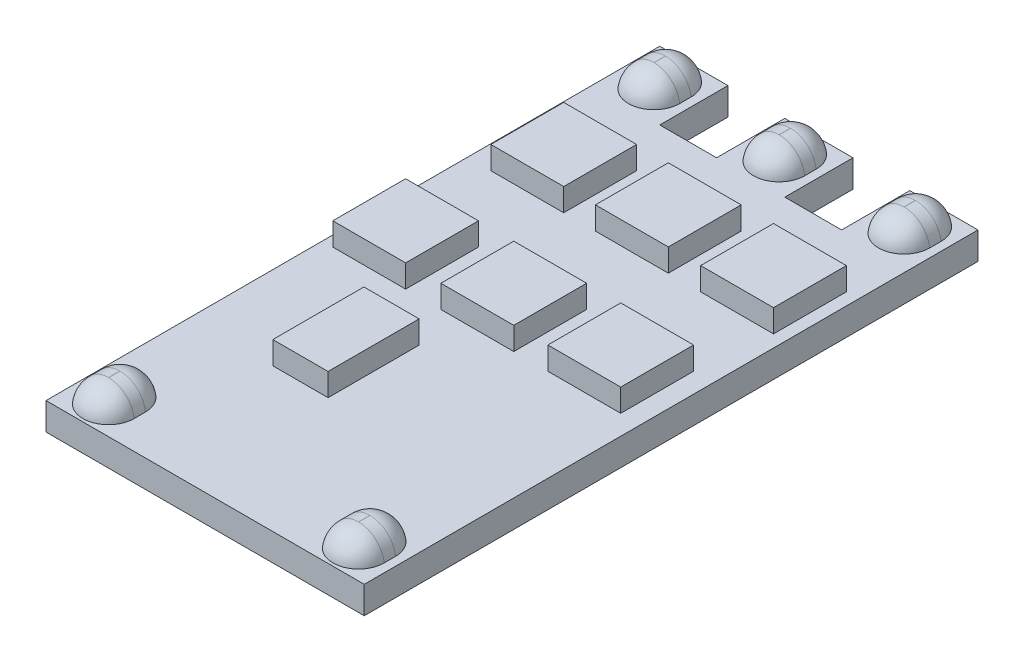
SolidWorks part; units mm, degrees
ref_plane "Front Plane" through (0, 0, 0) normal (0, 0, 1) x (1, 0, 0)
ref_plane "Top Plane" through (0, 0, 0) normal (0, 1, 0) x (1, 0, 0)
ref_plane "Right Plane" through (0, 0, 0) normal (1, 0, 0) x (0, 0, -1)
sketch "Sketch1" plane through (0, 0, 0) normal (0, 1, 0) x (1, 0, 0)
  line L0 (0, 21.6721) -> (0, -24.4888) construction
  line L1 (-7, 12) -> (7, 12)
  line L2 (-7, 12) -> (-7, -12)
  line L3 (-7, -12) -> (7, -12)
  line L4 (7, 12) -> (7, -12)
  line L5 (-7, 12) -> (7, -12) construction
  line L6 (-7, -12) -> (7, 12) construction
  line L8 (-1.5, 15) -> (1.5, 15)
  line L9 (-1.5, 15) -> (-1.5, 12)
  line L10 (-1.5, 12) -> (1.5, 12)
  line L11 (1.5, 15) -> (1.5, 12)
  line L12 (-1.5, 15) -> (1.5, 12) construction
  line L13 (-1.5, 12) -> (1.5, 15) construction
  line L14 (-7, 12) -> (-4, 12)
  line L15 (-7, 12) -> (-7, 15)
  line L16 (-7, 15) -> (-4, 15)
  line L17 (-4, 12) -> (-4, 15)
  line L18 (7, 12) -> (4, 12)
  line L19 (7, 12) -> (7, 15)
  line L20 (7, 15) -> (4, 15)
  line L21 (4, 12) -> (4, 15)
  point P0 (0, 0)
  point P7 (0, 13.5)
  dimension "D1" = 24
  dimension "D2" = 14
  dimension "D3" = 3
  dimension "D4" = 3
extrude "PCB" add sketch "Sketch1" along normal blind 1.2 contours L4 L1 L2 L3 | L1 L17 L16 L15 | L11 L8 L9 L1 | L21 L1 L19 L20 region at (-5.5, 0, -13.5) region at (0, 0, 0) region at (0, 0, -13.5) region at (5.5, 0, -13.5)
sketch "Sketch5" plane through (0, 1.2, 0) normal (0, 1, 0) x (1, 0, 0)
  line L0 (-7, 12) -> (7, 12) construction
  line L1 (-7, 15) -> (-7, -12) construction
  line L2 (7, 15) -> (7, -12) construction
  line L3 (-4, 12) -> (-1.5, 12) construction
  line L4 (-5.5, 15) -> (-5.5, 12) construction
  line L5 (-7, 15) -> (-4, 15) construction
  line L6 (-7, 13.5) -> (7, 13.5) construction
  line L7 (0, 15) -> (0, 12) construction
  line L8 (-1.5, 15) -> (1.5, 15) construction
  line L9 (5.5, 15) -> (5.5, 12) construction
  line L10 (7, 15) -> (4, 15) construction
  line L11 (-5.5, 13.25) -> (-5.5, 13.75) construction
  line L12 (-6.625, 13.25) -> (-6.625, 13.75)
  line L13 (-4.375, 13.25) -> (-4.375, 13.75)
  line L14 (0, 13.75) -> (0, 13.25) construction
  line L15 (1.125, 13.75) -> (1.125, 13.25)
  line L16 (-1.125, 13.75) -> (-1.125, 13.25)
  line L17 (5.5, 13.75) -> (5.5, 13.25) construction
  line L18 (6.625, 13.75) -> (6.625, 13.25)
  line L19 (4.375, 13.75) -> (4.375, 13.25)
  line L20 (-4, 12) -> (-4, 15) construction
  line L21 (-7, -12) -> (7, -12)
  line L22 (-7, -12) -> (-7, -9)
  line L23 (-7, -9) -> (7, -9)
  line L24 (7, -12) -> (7, -9)
  line L25 (-7, -9) -> (-4, -9)
  line L26 (-7, -9) -> (-7, -12)
  line L27 (-7, -12) -> (-4, -12)
  line L28 (-4, -9) -> (-4, -12)
  line L29 (-5.5, -9) -> (-5.5, -12) construction
  line L30 (-5.5, -10.25) -> (-5.5, -10.75) construction
  line L31 (-4.375, -10.25) -> (-4.375, -10.75)
  line L32 (-6.625, -10.25) -> (-6.625, -10.75)
  line L33 (0, -9) -> (0, -12) construction
  line L34 (5.5, -10.25) -> (5.5, -10.75) construction
  line L35 (4.375, -10.25) -> (4.375, -10.75)
  line L36 (6.625, -10.25) -> (6.625, -10.75)
  arc A0 (-6.625, 13.25) -> (-4.375, 13.25) centre (-5.5, 13.25) ccw
  arc A1 (-4.375, 13.75) -> (-6.625, 13.75) centre (-5.5, 13.75) ccw
  arc A2 (1.125, 13.75) -> (-1.125, 13.75) centre (0, 13.75) ccw
  arc A3 (-1.125, 13.25) -> (1.125, 13.25) centre (0, 13.25) ccw
  arc A4 (6.625, 13.75) -> (4.375, 13.75) centre (5.5, 13.75) ccw
  arc A5 (4.375, 13.25) -> (6.625, 13.25) centre (5.5, 13.25) ccw
  arc A6 (-4.375, -10.25) -> (-6.625, -10.25) centre (-5.5, -10.25) ccw
  arc A7 (-6.625, -10.75) -> (-4.375, -10.75) centre (-5.5, -10.75) ccw
  arc A8 (4.375, -10.25) -> (6.625, -10.25) centre (5.5, -10.25) cw
  arc A9 (6.625, -10.75) -> (4.375, -10.75) centre (5.5, -10.75) cw
  point P14 (-5.5, 13.5)
  point P25 (-5.5, 13.5)
  point P32 (0, 13.5)
  point P39 (5.5, 13.5)
  point P57 (-5.5, -10.5)
  point P66 (5.5, -10.5)
  dimension "D1" = 2.25
  dimension "D2" = 0.5
  dimension "D3" = 3
extrude "Solder joints" add sketch "Sketch5" along normal blind 1 contours L13 A1 L12 A0 | L16 A3 L15 A2 | L19 A5 L18 A4 | L32 A7 L31 A6 | A9 L36 A8 L35 region at (-5.5, 1.2, -13.5) region at (0, 1.2, -13.5) region at (5.5, 1.2, -13.5) region at (-5.5, 1.2, 10.5) region at (5.5, 1.2, 10.5)
fillet "Solder fillets" radius 1.125 20 edges at (-5.5, 2.2, 9.125) (-4.375, 2.2, 10.5) (-5.5, 2.2, 11.875) (-6.625, 2.2, 10.5) (4.375, 2.2, 10.5) (5.5, 2.2, 9.125) (6.625, 2.2, 10.5) (5.5, 2.2, 11.875) (5.5, 2.2, -14.875) (6.625, 2.2, -13.5) (5.5, 2.2, -12.125) (4.375, 2.2, -13.5) (0, 2.2, -14.875) (1.125, 2.2, -13.5) (0, 2.2, -12.125) (-1.125, 2.2, -13.5) (-5.5, 2.2, -12.125) (-6.625, 2.2, -13.5) (-5.5, 2.2, -14.875) (-4.375, 2.2, -13.5)
sketch "Sketch2" plane through (0, 1.2, 0) normal (0, 1, 0) x (1, 0, 0)
  line L1 (-5.9719, 9.747) -> (-2.7662, 9.747)
  line L2 (-5.9719, 9.747) -> (-5.9719, 6.5413)
  line L3 (-5.9719, 6.5413) -> (-2.7662, 6.5413)
  line L4 (-2.7662, 9.747) -> (-2.7662, 6.5413)
  line L5 (-1.3702, 9.747) -> (1.8355, 9.747)
  line L6 (-1.3702, 9.747) -> (-1.3702, 6.5413)
  line L7 (-1.3702, 6.5413) -> (1.8355, 6.5413)
  line L8 (1.8355, 9.747) -> (1.8355, 6.5413)
  line L9 (3.2574, 9.747) -> (6.4631, 9.747)
  line L10 (3.2574, 9.747) -> (3.2574, 6.5413)
  line L11 (3.2574, 6.5413) -> (6.4631, 6.5413)
  line L12 (6.4631, 9.747) -> (6.4631, 6.5413)
  line L13 (-3.335, 3.3614) -> (-6.5407, 3.3614)
  line L14 (-3.335, 3.3614) -> (-3.335, 0.1557)
  line L15 (-3.335, 0.1557) -> (-6.5407, 0.1557)
  line L16 (-6.5407, 3.3614) -> (-6.5407, 0.1557)
  line L17 (-1.7838, 3.3614) -> (1.4219, 3.3614)
  line L18 (-1.7838, 3.3614) -> (-1.7838, 0.1557)
  line L19 (-1.7838, 0.1557) -> (1.4219, 0.1557)
  line L20 (1.4219, 3.3614) -> (1.4219, 0.1557)
  line L21 (2.9213, 3.3614) -> (6.1271, 3.3614)
  line L22 (2.9213, 3.3614) -> (2.9213, 0.1557)
  line L23 (2.9213, 0.1557) -> (6.1271, 0.1557)
  line L24 (6.1271, 3.3614) -> (6.1271, 0.1557)
  line L25 (-3.335, -1.6799) -> (-0.9048, -1.6799)
  line L26 (-3.335, -1.6799) -> (-3.335, -5.687)
  line L27 (-3.335, -5.687) -> (-0.9048, -5.687)
  line L28 (-0.9048, -1.6799) -> (-0.9048, -5.687)
extrude "Top components" add sketch "Sketch2" along normal blind 1
sketch "Sketch3" plane through (0, 0, 0) normal (0, -1, 0) x (1, 0, 0)
  line L1 (-2.7921, 0) -> (1.2409, 0)
  line L2 (-2.7921, 0) -> (-2.7921, 4.0583)
  line L3 (-2.7921, 4.0583) -> (1.2409, 4.0583)
  line L4 (1.2409, 0) -> (1.2409, 4.0583)
  line L5 (-5.8944, -3.9818) -> (-2.7921, -3.9818)
  line L6 (-5.8944, -3.9818) -> (-5.8944, -6.9032)
  line L7 (-5.8944, -6.9032) -> (-2.7921, -6.9032)
  line L8 (-2.7921, -3.9818) -> (-2.7921, -6.9032)
  line L9 (-1.3185, -3.9818) -> (1.4995, -3.9818)
  line L10 (-1.3185, -3.9818) -> (-1.3185, -6.9032)
  line L11 (-1.3185, -6.9032) -> (1.4995, -6.9032)
  line L12 (1.4995, -3.9818) -> (1.4995, -6.9032)
  line L13 (3.0765, -3.9818) -> (5.9461, -3.9818)
  line L14 (3.0765, -3.9818) -> (3.0765, -6.9032)
  line L15 (3.0765, -6.9032) -> (5.9461, -6.9032)
  line L16 (5.9461, -3.9818) -> (5.9461, -6.9032)
  line L17 (3.516, 9.4874) -> (5.3515, 9.4874)
  line L18 (3.516, 9.4874) -> (3.516, 6.3592)
  line L19 (3.516, 6.3592) -> (5.3515, 6.3592)
  line L20 (5.3515, 9.4874) -> (5.3515, 6.3592)
extrude "Bottom components" add sketch "Sketch3" along normal blind 1
